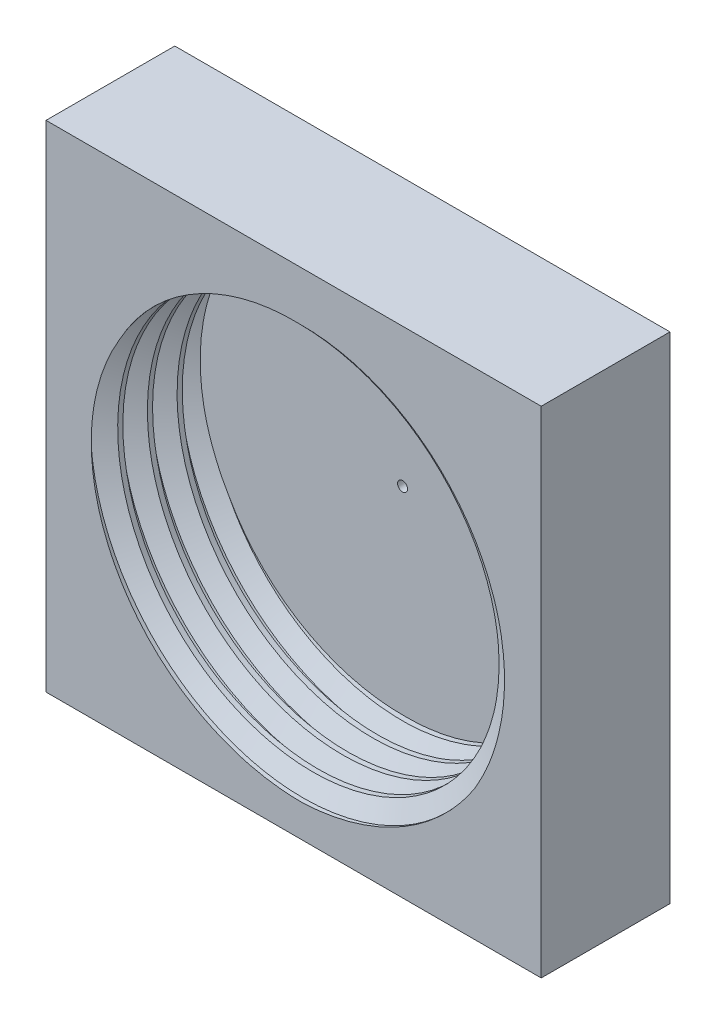
SolidWorks part; units mm, degrees
ref_plane "Front Plane" through (0, 0, 0) normal (0, 0, 1) x (1, 0, 0)
ref_plane "Top Plane" through (0, 0, 0) normal (0, 1, 0) x (1, 0, 0)
ref_plane "Right Plane" through (0, 0, 0) normal (1, 0, 0) x (0, 0, -1)
sketch "Sketch1" plane through (0, 0, 0) normal (0, 0, 1) x (1, 0, 0)
  line L0 (19.71, -19.71) -> (25, -25) construction
  line L1 (-25, 25) -> (25, 25)
  line L2 (-25, 25) -> (-25, -25)
  line L3 (-25, -25) -> (25, -25)
  line L4 (25, 25) -> (25, -25)
  line L5 (-25, 25) -> (0, 0) construction
  line L6 (-25, -25) -> (25, 25) construction
  circle A0 centre (0, 0) radius 20
  point P5 (0, 0)
  dimension "D1" = 40
  dimension "D2" = 50
  dimension "D3" = 50
extrude "Boss-Extrude1" add sketch "Sketch1" along normal blind 11
sketch "Sketch2" plane through (0, 0, 0) normal (0, 0, 1) x (1, 0, 0)
  line L1 (25, 25) -> (-25, 25)
  line L2 (25, 25) -> (25, -25)
  line L3 (25, -25) -> (-25, -25)
  line L4 (-25, 25) -> (-25, -25)
  line L5 (25, 25) -> (-25, -25) construction
  line L6 (25, -25) -> (-25, 25) construction
  point P0 (0, 0)
extrude "Boss-Extrude2" add sketch "Sketch2" against normal blind 2
sketch "Sketch9" plane through (0, 0, 0) normal (0, 1, 0) x (1, 0, 0)
  line L0 (0, 2) -> (0, -8) construction
  line L1 (-25, 2) -> (25, 2) construction
sketch "Sketch11" plane through (0, 0, 0) normal (0, 0, 1) x (1, 0, 0)
  circle A0 centre (0, 0) radius 0.5
  dimension "D1" = 1
extrude "Cut-Extrude3" cut sketch "Sketch11" against normal through all
ref_plane "Plane1" through (0, 0, 11) normal (0, 0, 1) x (1, 0, 0)
sketch "Sketch12" plane through (0, 0, 11) normal (0, 0, 1) x (1, 0, 0)
  circle A0 centre (0, 0) radius 20
curve "Helix/Spiral1" pitch 3 height 11 radius 20 centre (0, 0, 11) axis (0, 0, -1) start towards (0.5, 0.866, 0)
sketch "Sketch14" plane through (0, 0, 0) normal (0, 1, 0) x (1, 0, 0)
  line L0 (-19.9994, 0.2397) -> (-19.9994, -2.24)
  line L1 (-19.9994, -2.0626) -> (-21.4993, -1.1966) construction
  line L2 (-19.9994, -2.24) -> (-21.7494, -1.2296)
  line L3 (-21.7494, -1.2296) -> (-21.7494, -0.7706)
  line L4 (-21.7494, -0.7706) -> (-19.9994, 0.2397)
  line L5 (-21.7494, -1.0001) -> (-19.9994, -1.0001) construction
  line L6 (-21.4993, -1.1966) -> (-21.4993, -0.8036) construction
  line L7 (-21.4993, -0.8036) -> (-19.9994, 0.0624) construction
  line L8 (-20.7494, -1.6296) -> (-20.7494, -1.807) construction
  line L9 (-20.7494, -0.3706) -> (-20.7494, -0.1933) construction
  point P13 (0, 0)
  point P14 (0, 0)
  point P15 (0, 0)
  point P16 (0, 0)
  point P17 (0, 0)
  point P18 (0, 0)
  dimension "D1" = 1.75
  dimension "D2" = 60
sweep "Cut-Sweep1" cut profiles "Sketch14" path "Helix/Spiral1" align with end faces yes
